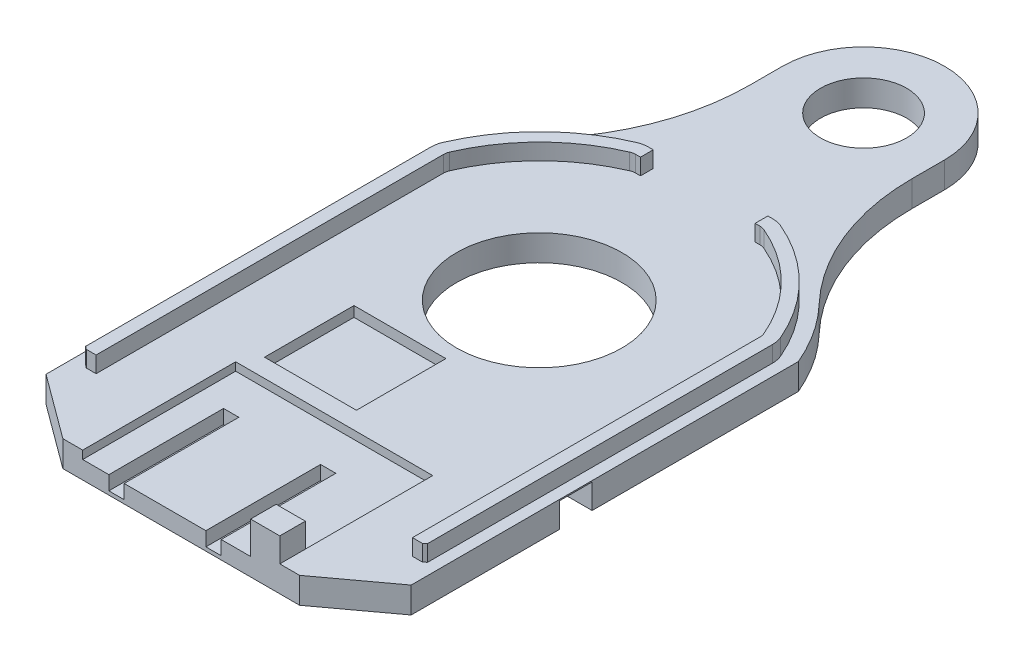
SolidWorks part; units mm, degrees
ref_plane "Front Plane" through (0, 0, 0) normal (0, 0, 1) x (1, 0, 0)
ref_plane "Top Plane" through (0, 0, 0) normal (0, 1, 0) x (1, 0, 0)
ref_plane "Right Plane" through (0, 0, 0) normal (1, 0, 0) x (0, 0, -1)
sketch "Sketch1" plane through (0, 0, 0) normal (0, 1, 0) x (1, 0, 0)
  line L0 (-14.3002, 5.9944) -> (-14.3002, -24.3332)
  line L1 (-14.3002, -24.3332) -> (-9.271, -28.0416)
  line L2 (-9.271, -28.0416) -> (9.271, -28.0416)
  line L3 (9.271, -28.0416) -> (14.3002, -24.3332)
  line L4 (14.3002, -24.3332) -> (14.3002, 5.9944)
  circle A0 centre (0, 0) radius 6.477
  arc A1 (-14.3002, 5.9944) -> (14.3002, 5.9944) centre (0, 0) cw
  dimension "D1" = 12.954
  dimension "D2" = 14.3002
  dimension "D3" = 14.3002
  dimension "D4" = 28.0416
  dimension "D5" = 5.0292
  dimension "D6" = 3.7084
  dimension "D7" = 3.7084
  dimension "D8" = 5.0292
  dimension "D9" = 34.036
extrude "Boss-Extrude1" add sketch "Sketch1" along normal blind 2.032
sketch "Sketch2" plane through (0, 2.032, 0) normal (0, 1, 0) x (1, 0, 0)
  line L0 (0, -28.0416) -> (-7.7191, -28.0416)
  line L1 (-9.271, -28.0416) -> (9.271, -28.0416) construction
  line L2 (0, -28.0416) -> (7.7191, -28.0416)
  line L3 (-7.7191, -28.0416) -> (-7.7191, -16.0604)
  line L4 (-7.7191, -16.0604) -> (7.7191, -16.0604)
  line L5 (7.7191, -16.0604) -> (7.7191, -28.0416)
  dimension "D1" = 7.7191
  dimension "D2" = 7.7191
  dimension "D3" = 11.9812
extrude "Cut-Extrude1" cut sketch "Sketch2" against normal blind 0.6401
sketch "Sketch3" plane through (0, 1.3919, 0) normal (0, 1, 0) x (1, 0, 0)
  line L0 (-7.7191, -28.0416) -> (7.7191, -28.0416) construction
  line L1 (-5.6693, -28.0416) -> (-4.4704, -28.0416)
  line L2 (-5.6693, -28.0416) -> (-5.6693, -19.0602)
  line L3 (-5.6693, -19.0602) -> (-4.4704, -19.0602)
  line L4 (-4.4704, -28.0416) -> (-4.4704, -19.0602)
  line L5 (-7.7191, -16.0604) -> (-7.7191, -28.0416) construction
  line L6 (1.9304, -28.0416) -> (3.1293, -28.0416)
  line L7 (1.9304, -28.0416) -> (1.9304, -19.0602)
  line L8 (1.9304, -19.0602) -> (3.1293, -19.0602)
  line L9 (3.1293, -28.0416) -> (3.1293, -19.0602)
  dimension "D1" = 2.0498
  dimension "D2" = 1.1989
  dimension "D3" = 6.4008
  dimension "D4" = 1.1989
  dimension "D5" = 8.9814
  dimension "D6" = 8.9814
extrude "Cut-Extrude2" cut sketch "Sketch3" against normal blind 1.0998
sketch "Sketch4" plane through (0, 2.032, 0) normal (0, 1, 0) x (1, 0, 0)
  line L0 (-7.7191, -16.0604) -> (-7.7191, -28.0416) construction
  line L1 (-6.8991, -14.6205) -> (0.2992, -14.6205)
  line L2 (-6.8991, -14.6205) -> (-6.8991, -7.6126)
  line L3 (-6.8991, -7.6126) -> (0.2992, -7.6126)
  line L4 (0.2992, -14.6205) -> (0.2992, -7.6126)
  line L5 (7.7191, -16.0604) -> (-7.7191, -16.0604) construction
  dimension "D1" = 0.8199
  dimension "D2" = 1.4399
  dimension "D3" = 7.0079
  dimension "D4" = 7.1984
extrude "Cut-Extrude3" cut sketch "Sketch4" against normal blind 0.8001
sketch "Sketch5" plane through (0, 2.032, 0) normal (0, 1, 0) x (1, 0, 0)
  line L0 (12.4028, -22.3342) -> (13.1717, -22.3342)
  line L1 (13.1717, -22.3342) -> (13.401, -22.1529)
  line L2 (13.401, -22.1529) -> (13.401, 4.8829)
  line L3 (12.4028, -22.3342) -> (12.4028, 4.8819)
  line L4 (7.7191, -28.0416) -> (9.271, -28.0416) construction
  line L5 (14.3002, -24.3332) -> (14.3002, 5.9944) construction
  line L6 (4.8793, 13.401) -> (4.5034, 13.401)
  line L7 (4.5034, 13.401) -> (4.5034, 12.4028)
  line L8 (4.5034, 12.4028) -> (4.8793, 12.4028)
  line L9 (0.0143, 14.8202) -> (0.0143, -25.5245) construction
  line L10 (-4.8508, 13.401) -> (-4.4748, 13.401)
  line L11 (-4.4748, 13.401) -> (-4.4748, 12.4028)
  line L12 (-4.4748, 12.4028) -> (-4.8508, 12.4028)
  line L13 (-12.3742, -22.3342) -> (-12.3742, 4.8819)
  line L14 (-12.3742, -22.3342) -> (-13.1431, -22.3342)
  line L15 (-13.1431, -22.3342) -> (-13.3725, -22.1529)
  line L16 (-13.3725, -22.1529) -> (-13.3725, 4.8829)
  arc A0 (5.2725, 12.3222) -> (12.3222, 5.2751) centre (0.0143, 0.0124) cw
  arc A1 (4.8793, 12.4028) -> (5.2725, 12.3222) centre (4.8793, 11.404) cw
  arc A2 (12.4028, 4.8819) -> (12.3222, 5.2751) centre (11.404, 4.8819) ccw
  arc A3 (5.6081, 13.2644) -> (13.2397, 5.6678) centre (0.0024, 0.0011) cw
  arc A4 (4.8793, 13.401) -> (5.6081, 13.2644) centre (4.8793, 11.3897) cw
  arc A5 (13.2397, 5.6678) -> (13.401, 4.8829) centre (11.4022, 4.8811) cw
  arc A6 (-5.5795, 13.2644) -> (-13.2112, 5.6678) centre (0.0262, 0.0011) ccw
  arc A7 (-4.8508, 13.401) -> (-5.5795, 13.2644) centre (-4.8508, 11.3897) ccw
  arc A8 (-4.8508, 12.4028) -> (-5.2439, 12.3222) centre (-4.8508, 11.404) ccw
  arc A9 (-5.2439, 12.3222) -> (-12.2936, 5.2751) centre (0.0143, 0.0124) ccw
  arc A10 (-12.3742, 4.8819) -> (-12.2936, 5.2751) centre (-11.3754, 4.8819) cw
  arc A11 (-13.2112, 5.6678) -> (-13.3725, 4.8829) centre (-11.3736, 4.8811) ccw
  dimension "D17" = 13.3858
  dimension "D22" = 14.3993
  dimension "D1" = 5.7074
  dimension "D2" = 0.2294
  dimension "D3" = 0.1814
  dimension "D4" = 0.8992
  dimension "D5" = 0.9982
  dimension "D6" = 27.2161
  dimension "D7" = 27.0358
  dimension "D8" = 7.8994
  dimension "D9" = 7.5209
  dimension "D10" = 0.9982
  dimension "D11" = 0.3759
  dimension "D12" = 0.3759
  dimension "D13" = 0.3932
  dimension "D14" = 0.0806
  dimension "D15" = 0.3932
  dimension "D16" = 0.0806
  dimension "D18" = 0.7287
  dimension "D19" = 0.1367
  dimension "D20" = 0.1613
  dimension "D21" = 0.7849
extrude "Boss-Extrude2" add sketch "Sketch5" along normal blind 1.27
sketch "Sketch6" plane through (0, 1.3919, 0) normal (0, 1, 0) x (1, 0, 0)
  line L1 (7.7191, -28.0416) -> (5.4331, -28.0416)
  line L2 (7.7191, -28.0416) -> (7.7191, -26.0426)
  line L3 (7.7191, -26.0426) -> (5.4331, -26.0426)
  line L4 (5.4331, -28.0416) -> (5.4331, -26.0426)
  dimension "D1" = 2.286
  dimension "D2" = 1.999
extrude "Boss-Extrude3" add sketch "Sketch6" along normal blind 2.54
sketch "Sketch7" plane through (0, 0, 0) normal (0, -1, 0) x (1, 0, 0)
  line L0 (-6.35, -25.4) -> (-6.35, -22.86)
  line L1 (6.35, -25.4) -> (6.35, -22.86)
  circle A0 centre (0, -25.4) radius 3.3734
  arc A1 (-6.35, -25.4) -> (6.35, -25.4) centre (0, -25.4) ccw
  arc A3 (-11.2188, -10.7036) -> (11.2188, -10.7036) centre (0, 0) ccw
  arc A4 (-6.35, -22.86) -> (-11.2188, -10.7036) centre (-23.9604, -22.86) ccw
  arc A5 (11.2188, -10.7036) -> (6.35, -22.86) centre (23.9604, -22.86) ccw
  dimension "D2" = 6.7469
  dimension "D3" = 12.7
  dimension "D4" = 2.54
  dimension "D1" = 25.4
  dimension "D5" = 2.54
extrude "Boss-Extrude4" add sketch "Sketch7" against normal up to surface (2.032 mm away) up to face at (9.3442, 2.032, -2.5052)
sketch "Sketch8" plane through (14.3002, 0, 0) normal (1, 0, 0) x (0, 0, -1)
  line L0 (-24.3332, 0) -> (5.9944, 0) construction
  line L1 (-10.16, 0) -> (-12.7, 0)
  line L2 (-10.16, 0) -> (-10.16, 0.7937)
  line L3 (-10.16, 0.7937) -> (-12.7, 0.7937)
  line L4 (-12.7, 0) -> (-12.7, 0.7937)
  dimension "D1" = 12.7
  dimension "D2" = 2.54
  dimension "D3" = 0.7937
extrude "Cut-Extrude4" cut sketch "Sketch8" against normal through all both and the other way through all
chamfer "Chamfer1" distance 1.143 angle 45 1 edges at (14.3002, 0.7937, 11.43)
chamfer "Chamfer2" distance 1.143 angle 45 1 edges at (-14.3002, 0.7937, 11.43)
